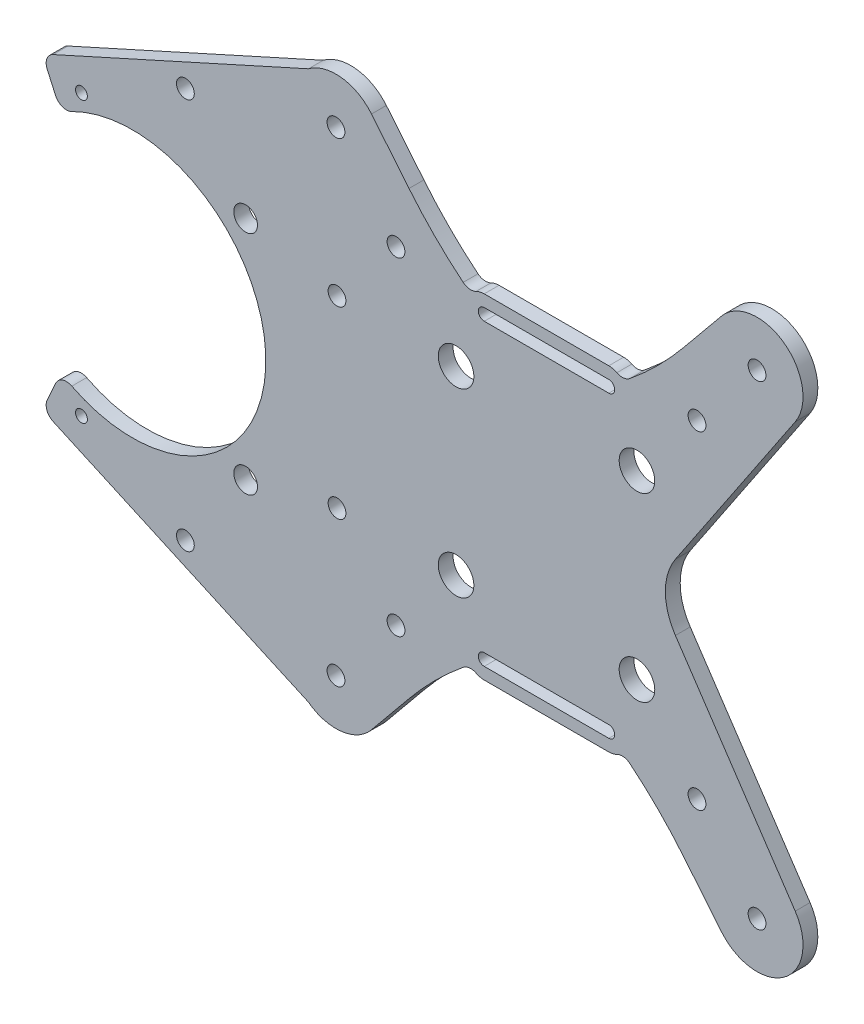
SolidWorks part; units mm, degrees
ref_plane "Alzado" through (0, 0, 0) normal (0, 0, 1) x (1, 0, 0)
ref_plane "Planta" through (0, 0, 0) normal (0, 1, 0) x (1, 0, 0)
ref_plane "Vista lateral" through (0, 0, 0) normal (1, 0, 0) x (0, 0, -1)
sketch "Croquis1" plane through (0, 0, 0) normal (0, 0, 1) x (1, 0, 0)
  line L0 (-29.5025, -44.95) -> (-23.1778, -37.2438)
  line L1 (29.5025, 44.95) -> (23.1778, 37.2438)
  line L2 (-10.5003, 28.196) -> (10.5003, 28.196)
  line L3 (10.4997, -24.196) -> (-10.5003, -24.196)
  line L4 (10.4997, 24.196) -> (-10.5003, 24.196)
  line L5 (23.1779, -37.2437) -> (29.5025, -44.95)
  line L6 (41.9317, 35.7196) -> (21.7292, 5.5661)
  line L7 (-10.5003, -28.196) -> (10.4997, -28.196)
  line L8 (-85.5141, -4.166) -> (-47.6698, -4.166) construction
  line L9 (-85.5141, 4.166) -> (-47.6698, 4.166) construction
  line L10 (-97.3181, -20) -> (-50.1355, -20)
  line L11 (-23.1779, 37.2437) -> (-29.5025, 44.95)
  line L12 (41.9317, -35.7196) -> (21.7292, -5.5661)
  line L13 (-97.3181, 20) -> (-50.1355, 20)
  line L14 (-10.5003, -26.196) -> (10.4997, -26.196)
  line L15 (-10.5003, 26.196) -> (10.4997, 26.196)
  arc A0 (21.7292, 5.5661) -> (21.7292, -5.5661) centre (30.037, 0) ccw
  circle A1 centre (-25.3716, 27.6416) radius 2.25
  arc A2 (41.9317, 35.7196) -> (29.5025, 44.95) centre (35.4932, 40.0333) ccw
  arc A3 (-41.8863, -35.6526) -> (-29.5025, -44.95) centre (-35.4932, -40.0333) ccw
  circle A4 centre (-35.4932, 40.0333) radius 2.25
  arc A5 (-41.8863, -35.6526) -> (-50.1355, -20) centre (-50.1355, -30) ccw
  circle A6 centre (-35.4932, -40.0333) radius 2.25
  arc A7 (14.0461, 28.0999) -> (23.1778, 37.2438) centre (-27.1528, 78.3757) ccw
  circle A8 centre (15.25, -15.25) radius 3
  arc A9 (-14.0461, 28.0999) -> (-11.8672, 27.8665) centre (-12.7784, 29.6469) ccw
  circle A10 centre (35.4932, -40.0333) radius 2.25
  arc A11 (14.0461, -28.0999) -> (11.8672, -27.8665) centre (12.7784, -29.6469) ccw
  circle A12 centre (-15.25, 15.25) radius 3
  arc A13 (10.4997, 24.196) -> (10.4997, 26.196) centre (10.4997, 25.196) ccw
  arc A14 (-47.6698, 4.166) -> (-46.6061, 8.9284) centre (-47.6698, 6.666) ccw construction
  circle A15 centre (-25.3716, -27.6416) radius 2.25
  arc A16 (-48.7757, -9.4863) -> (-46.6061, -8.9284) centre (-49.1589, -3.4986) ccw construction
  circle A17 centre (-35.3181, 15.5) radius 1.5
  arc A18 (-11.8672, -27.8665) -> (-10.5003, -28.196) centre (-10.5003, -25.196) ccw
  circle A19 centre (25.3716, -27.6416) radius 2.25
  arc A20 (-14.0461, -28.0999) -> (-23.1778, -37.2438) centre (27.1528, -78.3757) ccw
  arc A21 (29.5025, -44.95) -> (41.9317, -35.7196) centre (35.4932, -40.0333) ccw
  arc A22 (11.8672, 27.8665) -> (14.0461, 28.0999) centre (12.7784, 29.6469) ccw
  arc A23 (10.4997, -28.196) -> (11.8672, -27.8665) centre (10.5003, -25.196) ccw
  arc A24 (-10.5003, -24.196) -> (-10.5003, -26.196) centre (-10.5003, -25.196) ccw
  circle A25 centre (-15.25, -15.25) radius 3
  circle A26 centre (-97.3181, 15.5) radius 1.5
  arc A27 (-46.6061, -8.9284) -> (-47.6698, -4.166) centre (-47.6698, -6.666) ccw construction
  circle A28 centre (15.25, 15.25) radius 3
  arc A29 (-50.1355, 20) -> (-41.8863, 35.6526) centre (-50.1355, 30) ccw
  arc A30 (-11.8672, -27.8665) -> (-14.0461, -28.0999) centre (-12.7784, -29.6469) ccw
  circle A31 centre (-35.3181, -15.5) radius 1.5
  arc A32 (-10.5003, 26.196) -> (-10.5003, 24.196) centre (-10.5003, 25.196) ccw
  circle A33 centre (25.3716, 27.6416) radius 2.25
  arc A34 (-88.511, 7.03) -> (-85.5141, 4.166) centre (-85.5141, 7.166) ccw construction
  arc A35 (-88.511, -7.03) -> (-81.5427, -13.2223) centre (-82.5172, -7.302) ccw construction
  arc A36 (-10.5003, 28.196) -> (-11.8672, 27.8665) centre (-10.5003, 25.196) ccw
  circle A37 centre (-97.3181, -15.5) radius 1.5
  arc A38 (-97.3181, 20) -> (-100.6815, 18.3128) centre (-97.3181, 15.804) ccw
  arc A39 (-81.5427, 13.2223) -> (-48.7757, 9.4863) centre (-27.5409, 341.2912) ccw construction
  arc A40 (-81.5427, 13.2223) -> (-88.511, 7.03) centre (-82.5172, 7.302) ccw construction
  arc A41 (11.8672, 27.8665) -> (10.5003, 28.196) centre (10.5003, 25.196) ccw
  arc A42 (-48.7757, -9.4863) -> (-81.5427, -13.2223) centre (-27.5408, -341.2912) ccw construction
  arc A43 (-85.5141, -4.166) -> (-88.511, -7.03) centre (-85.5141, -7.166) ccw construction
  arc A44 (23.1779, -37.2437) -> (14.0461, -28.0999) centre (-27.1523, -78.3761) ccw
  circle A45 centre (35.4932, 40.0333) radius 2.25
  arc A46 (-46.6061, 8.9284) -> (-48.7757, 9.4863) centre (-49.1589, 3.4986) ccw construction
  arc A47 (10.4997, -26.196) -> (10.4997, -24.196) centre (10.4997, -25.196) ccw
  arc A48 (-29.5025, 44.95) -> (-41.8863, 35.6526) centre (-35.4932, 40.0333) ccw
  arc A49 (-23.1779, 37.2437) -> (-14.0461, 28.0999) centre (27.1523, 78.3761) ccw
  arc A50 (-100.6815, -18.3128) -> (-97.3181, -20) centre (-97.3181, -15.804) ccw
  spline S0 degree 3 poles (-107.3181, 0) (-107.2524, 7.0597) (-104.9757, 13.1646) (-100.6815, 18.3128) knots 0 0 0 0 1 1 1 1
  spline S1 degree 3 poles (-107.3181, 0) (-107.2524, -7.0597) (-104.9757, -13.1646) (-100.6815, -18.3128) knots 0 0 0 0 1 1 1 1
  dimension "D1" = 47.1826
extrude "Saliente-Extruir1" add sketch "Croquis1" along normal blind 2.5
sketch "Croquis6" plane through (0, 0, 2.5) normal (0, 0, 1) x (1, 0, 0)
  line L0 (-99.1995, 19.5546) -> (-40.1463, 46.231)
  line L2 (-107.3181, 0) -> (-91.4281, 0) construction
  line L8 (-50.1355, 20) -> (-97.3181, 20)
  line L11 (-50.1355, -20) -> (-97.3181, -20)
  line L12 (-99.1995, -19.5546) -> (-40.1463, -46.231)
  line L13 (0, 0) -> (0, 40.0333) construction
  line L14 (0, 0) -> (37.562, 0) construction
  arc A2 (-29.5025, 44.95) -> (-41.8863, 35.6526) centre (-35.4932, 40.0333) ccw construction
  arc A3 (-40.1463, 46.231) -> (-41.8863, 35.6526) centre (-35.4932, 40.0333) ccw
  arc A7 (-97.3181, 20) -> (-100.6815, 18.3128) centre (-97.3181, 15.804) ccw construction
  arc A12 (-50.1355, 20) -> (-41.8863, 35.6526) centre (-50.1355, 30) ccw
  arc A16 (-99.1995, 19.5546) -> (-97.3181, 20) centre (-98.7978, 22.0539) ccw
  arc A17 (-99.1995, -19.5546) -> (-97.3181, -20) centre (-98.7978, -22.0539) cw
  arc A18 (-50.1355, -20) -> (-41.8863, -35.6526) centre (-50.1355, -30) cw
  arc A19 (-40.1463, -46.231) -> (-41.8863, -35.6526) centre (-35.4932, -40.0333) cw
  circle A20 centre (-35.4932, 40.0333) radius 2.25
  circle A21 centre (-35.4932, 40.0333) radius 1.5
  circle A22 centre (-25.3716, 27.6416) radius 2.25
  circle A23 centre (-25.3716, 27.6416) radius 1.5
  circle A24 centre (25.3716, 27.6416) radius 1.5
  circle A25 centre (25.3716, 27.6416) radius 2.25
  circle A26 centre (35.4932, 40.0333) radius 1.5
  circle A27 centre (35.4932, 40.0333) radius 2.25
  circle A28 centre (35.4932, -40.0333) radius 2.25
  circle A29 centre (35.4932, -40.0333) radius 1.5
  circle A30 centre (25.3716, -27.6416) radius 2.25
  circle A31 centre (25.3716, -27.6416) radius 1.5
  circle A32 centre (-25.3716, -27.6416) radius 1.5
  circle A33 centre (-25.3716, -27.6416) radius 2.25
  circle A34 centre (-35.4932, -40.0333) radius 1.5
  circle A35 centre (-35.4932, -40.0333) radius 2.25
  dimension "D1" = 3
  dimension "D2" = 3
extrude "Saliente-Extruir3" add sketch "Croquis6" against normal up to vertex (2.5 mm away) up to point (-50.1355, -20, 0)
sketch "Croquis5" plane through (0, 0, 2.5) normal (0, 0, 1) x (1, 0, 0)
  line L1 (-69.8181, 0) -> (-78.4028, 23.5863) construction
  line L2 (-102.3181, -32.5) -> (-37.3181, -32.5) construction
  line L3 (-102.3181, -32.5) -> (-102.3181, 32.5) construction
  line L4 (-102.3181, 32.5) -> (-37.3181, 32.5) construction
  line L5 (-37.3181, -32.5) -> (-37.3181, 32.5) construction
  line L6 (-102.3181, -32.5) -> (-37.3181, 32.5) construction
  line L7 (-102.3181, 32.5) -> (-37.3181, -32.5) construction
  line L8 (-69.8181, 19) -> (-97.3181, 19) construction
  line L9 (-69.8181, -19) -> (-97.3181, -19) construction
  circle A0 centre (-69.8181, 0) radius 22.5
  circle A9 centre (-78.4028, 23.5863) radius 1
  circle A11 centre (-78.4028, 23.5863) radius 1.6 construction
  circle A15 centre (-69.8181, 0) radius 19 construction
  circle A16 centre (-69.8181, 0) radius 25.1 construction
  circle A18 centre (-94.9181, 0) radius 1
  circle A20 centre (-78.4028, -23.5863) radius 1
  circle A21 centre (-50.7262, 19.0919) radius 2
  circle A22 centre (-50.7262, -19.0919) radius 2
  circle A24 centre (-15.25, 15.25) radius 3 construction
  point P32 (-69.8181, 0)
  point P49 (-69.8181, 0)
  dimension "D1" = 45
  dimension "D9" = 2
  dimension "D10" = 4
  dimension "D15" = 2
  dimension "D16" = 3.2
  dimension "D5" = 25.1
  dimension "D7" = 38
  dimension "D8" = 27
  dimension "D2" = 54.5681
  dimension "D3" = 65
  dimension "D4" = 65
  dimension "D6" = 25
extrude "Cortar-Extruir5" cut sketch "Croquis5" against normal up to vertex (2.5 mm away) up to point (-100.6815, -18.3128, 0)
sketch "Croquis7" [suppressed] plane through (0, 0, 2.5) normal (0, 0, 1) x (1, 0, 0)
  line L0 (-94.8181, 13) -> (-94.8181, -13) construction
  line L1 (-94.8181, -13) -> (-92.3181, -13) construction
  line L2 (-94.8181, 13) -> (-95.2639, 10.5401) construction
  line L3 (-94.8181, -13) -> (-94.8181, -15.5) construction
  line L4 (-94.8181, -15.5) -> (-74.7678, -15.5)
  line L5 (-74.7678, -15.5) -> (-74.7678, -4.9497)
  line L6 (-74.7678, -4.9497) -> (-100.2237, -4.9497)
  line L7 (-100.2237, -4.9497) -> (-100.2237, -19.0919)
  line L8 (-98.8886, -19.695) -> (-40.1463, -46.231) construction
  line L9 (-100.2237, -19.0919) -> (-77.4195, -29.3934)
  line L10 (-77.4195, -29.3934) -> (-94.8181, -15.5)
  circle A0 centre (-94.8181, 13) radius 1.6
  circle A1 centre (-94.8181, -13) radius 1.6
  dimension "D4" = 3.2
  dimension "D5" = 3.2
  dimension "D1" = 2.5
  dimension "D2" = 2.5
  dimension "D3" = 2.5
sketch "Croquis9" plane through (0, 0, 2.5) normal (0, 0, 1) x (1, 0, 0)
  circle A0 centre (-97.3181, 15.5) radius 1.5
  circle A1 centre (-97.3181, -15.5) radius 1.5
  circle A2 centre (-35.3181, -15.5) radius 1.5
  circle A3 centre (-35.3181, 15.5) radius 1.5
sketch "Croquis10" plane through (0, 0, 2.5) normal (0, 0, 1) x (1, 0, 0)
  line L0 (-69.8181, 19) -> (-81.8573, 19.0081) construction
  line L1 (-81.8573, 19.0081) -> (-85.0015, 25.9683)
  line L2 (-40.1463, 46.231) -> (-98.8886, 19.695) construction
  line L3 (-69.8181, 0) -> (-92.3181, 0) construction
  line L4 (-92.3181, 0) -> (-107.3181, 0) construction
  line L5 (-81.8573, -19.0081) -> (-85.0015, -25.9683)
  circle A0 centre (-69.8181, 0) radius 19 construction
  circle A2 centre (-69.8181, 0) radius 22.5 construction
  arc A4 (-81.8573, 19.0081) -> (-81.8573, -19.0081) centre (-69.8181, 0) ccw
  arc A5 (-107.3181, 0) -> (-85.0015, 25.9683) centre (-87.1842, 5.2707) cw
  arc A6 (-107.3181, 0) -> (-85.0015, -25.9683) centre (-87.1842, -5.2707) ccw
  dimension "D1" = 38
extrude "Cortar-Extruir6" cut sketch "Croquis10" against normal up to vertex (2.5 mm away) up to point (-40.1463, -46.231, 0)
fillet "Redondeo1" radius 2 4 edges at (-81.8573, -19.0081, 1.25) (-85.0015, -25.9683, 1.25) (-85.0015, 25.9683, 1.25) (-81.8573, 19.0081, 1.25)
sketch "Croquis11" plane through (0, 0, 2.5) normal (0, 0, 1) x (1, 0, 0)
  line L0 (-60.8816, 32.9846) -> (-83.546, 22.7463) construction
  line L1 (-82.7607, 21.0077) -> (-84.1782, 24.1456) construction
  line L3 (-60.8816, -32.9846) -> (-62.3371, -36.2066) construction
  line L4 (-83.1789, -26.7916) -> (-40.1463, -46.231) construction
  circle A2 centre (-60.8816, 32.9846) radius 1.5
  circle A3 centre (-60.8816, -32.9846) radius 1.5
  dimension "D1" = 24.8697
  dimension "D2" = 3.5355
extrude "Cortar-Extruir7" cut sketch "Croquis11" against normal up to surface (2.5 mm away) up to face at (-77.4028, 23.5863, 0)
sketch "Croquis12" plane through (0, 0, 2.5) normal (0, 0, 1) x (1, 0, 0)
  line L2 (-47.3181, 0) -> (-43.3181, 0) construction
  line L3 (-43.3181, 0) -> (-43.3181, 44.7982) construction
  line L4 (-40.1463, 46.231) -> (-83.1789, 26.7916) construction
  line L5 (-43.3181, 44.7982) -> (-43.3181, -44.7982)
  line L6 (-83.1789, -26.7916) -> (-40.1463, -46.231) construction
  line L7 (-43.3181, -44.7982) -> (-142.4871, 0)
  line L8 (-142.4871, 0) -> (-43.3181, 44.7982)
  line L12 (-84.1782, 24.1456) -> (-82.7607, 21.0077)
  line L13 (-84.1782, 24.1456) -> (-82.7607, 21.0077)
  line L16 (-82.7607, -21.0077) -> (-84.1782, -24.1456)
  line L17 (-82.7607, -21.0077) -> (-84.1782, -24.1456)
  arc A11 (-80.0303, -20.049) -> (-80.0303, 20.049) centre (-69.8181, 0) ccw construction
  circle A12 centre (-60.8816, 32.9846) radius 1.5
  circle A13 centre (-78.4028, 23.5863) radius 1
  circle A14 centre (-78.4028, -23.5863) radius 1
  circle A15 centre (-60.8816, -32.9846) radius 1.5
  circle A16 centre (-69.8181, 0) radius 22.5
  circle A17 centre (-69.8181, 0) radius 22.5
  arc A24 (-83.1789, 26.7916) -> (-84.1782, 24.1456) centre (-82.3555, 24.969) ccw
  arc A25 (-82.7607, 21.0077) -> (-80.0303, 20.049) centre (-80.938, 21.8311) ccw
  arc A26 (-83.1789, 26.7916) -> (-84.1782, 24.1456) centre (-82.3555, 24.969) ccw
  arc A27 (-82.7607, 21.0077) -> (-80.0303, 20.049) centre (-80.938, 21.8311) ccw
  arc A32 (-80.0303, -20.049) -> (-82.7607, -21.0077) centre (-80.938, -21.8311) ccw
  arc A33 (-84.1782, -24.1456) -> (-83.1789, -26.7916) centre (-82.3555, -24.969) ccw
  arc A34 (-80.0303, -20.049) -> (-82.7607, -21.0077) centre (-80.938, -21.8311) ccw
  arc A35 (-84.1782, -24.1456) -> (-83.1789, -26.7916) centre (-82.3555, -24.969) ccw
  dimension "D1" = 4
  dimension "D2" = 0
  dimension "D3" = 0
  dimension "D4" = 0
